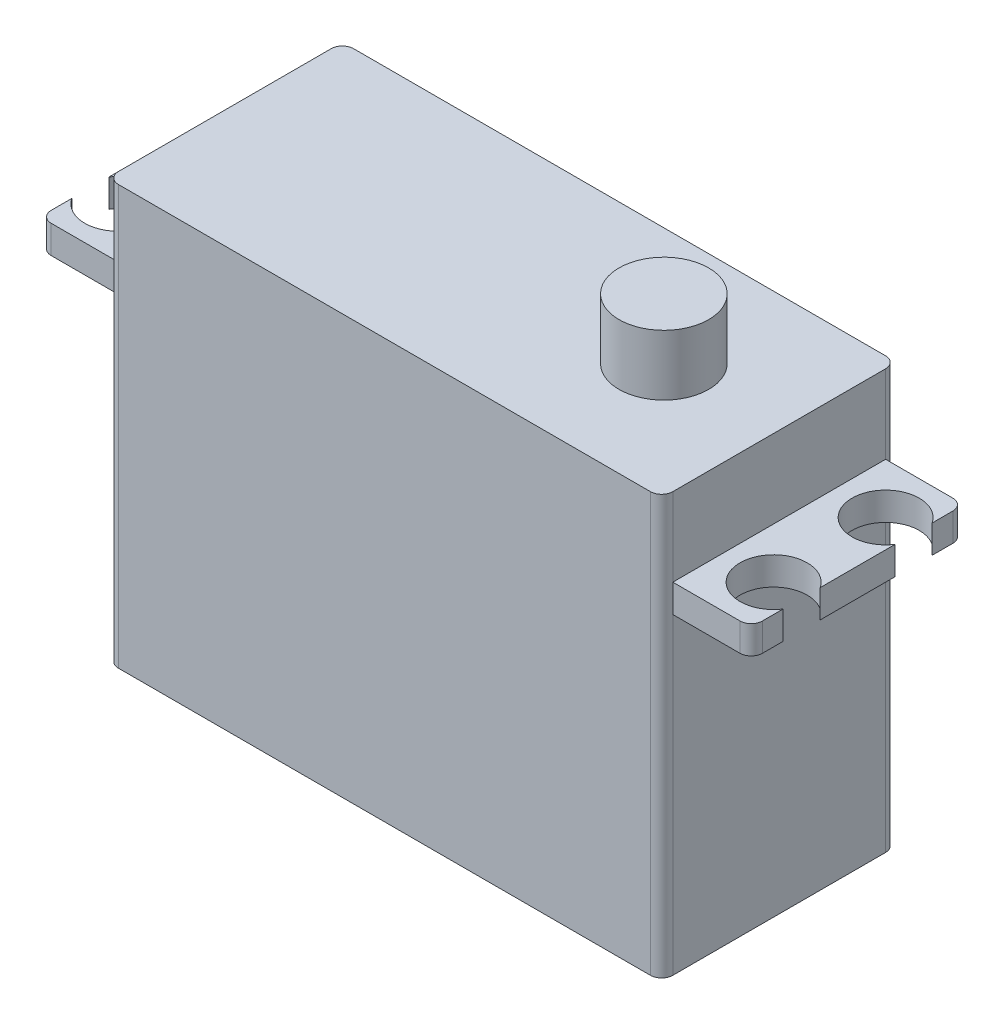
SolidWorks part; units mm, degrees
ref_plane "Front" through (0, 0, 0) normal (0, 0, 1) x (1, 0, 0)
ref_plane "Top" through (0, 0, 0) normal (0, 1, 0) x (1, 0, 0)
ref_plane "Right" through (0, 0, 0) normal (1, 0, 0) x (0, 0, -1)
sketch "草图1" plane through (0, 0, 0) normal (0, 1, 0) x (1, 0, 0)
  line L0 (0, 0) -> (0, 10.5) construction
  line L1 (-24.75, 10.5) -> (24.75, 10.5) construction
  line L2 (24.75, 10.5) -> (24.75, -10.5) construction
  line L3 (0, 0) -> (24.75, 0) construction
  line L4 (-24.75, 10.5) -> (-24.75, -10.5) construction
  line L5 (-24.75, -10.5) -> (24.75, -10.5) construction
  line L6 (-24.75, -10.5) -> (24.75, -10.5)
  line L7 (24.75, -10.5) -> (24.75, 10.5)
  line L8 (24.75, 10.5) -> (-24.75, 10.5)
  line L9 (-24.75, 10.5) -> (-24.75, -10.5)
  point P9 (-24.75, 0)
extrude "凸台-拉伸1" add sketch "草图1" along normal blind 30.4
sketch "草图2" plane through (24.75, 0, 0) normal (1, 0, 0) x (0, 0, -1)
  line L0 (0, 30.4) -> (0, 27.9) construction
  line L1 (-10.5, 30.4) -> (10.5, 30.4) construction
  line L2 (-9.5, 27.9) -> (9.5, 27.9) construction
  line L3 (-9.5, 27.9) -> (9.5, 27.9)
  line L4 (9.5, 27.9) -> (9.5, 30.4)
  line L5 (9.5, 30.4) -> (-9.5, 30.4)
  line L6 (-9.5, 30.4) -> (-9.5, 27.9)
extrude "凸台-拉伸2" add sketch "草图2" along normal blind 7
sketch "草图3" plane through (0, 30.4, 0) normal (0, 1, 0) x (1, 0, 0)
  line L0 (-24.75, 10.5) -> (-24.75, -10.5)
  line L1 (-24.75, -10.5) -> (24.75, -10.5)
  line L2 (24.75, -10.5) -> (24.75, 10.5)
  line L3 (24.75, 10.5) -> (-24.75, 10.5)
extrude "凸台-拉伸3" add sketch "草图3" along normal blind 7
sketch "草图4" plane through (0, 30.4, 0) normal (0, 1, 0) x (1, 0, 0)
  line L0 (24.75, 0) -> (31.75, 0) construction
  line L1 (24.75, -10.5) -> (24.75, 10.5) construction
  line L2 (31.75, 9.5) -> (31.75, -9.5) construction
  line L3 (24.75, 0) -> (24.75, 5) construction
  line L4 (24.75, -9.5) -> (24.75, 9.5) construction
  line L5 (24.75, 5) -> (29.25, 5) construction
  circle A0 centre (29.25, 5) radius 3
  circle A1 centre (29.25, -5) radius 3
extrude "切除-拉伸1" cut sketch "草图4" against normal blind 7
sketch "草图5" plane through (0, 37.4, 0) normal (0, 1, 0) x (1, 0, 0)
  line L0 (24.75, 0) -> (14.45, 0) construction
  line L1 (24.75, -10.5) -> (24.75, 10.5) construction
  circle A0 centre (14.45, 0) radius 4
extrude "凸台-拉伸4" add sketch "草图5" along normal blind 5.4
mirror "镜向2" about plane through (0, 0, 0) normal (1, 0, 0) of "切除-拉伸1", "凸台-拉伸2"
fillet "圆角1" radius 1 1 edges at (24.75, 18.7, -10.5)
fillet "圆角2" radius 1 1 edges at (24.75, 18.7, 10.5)
fillet "圆角3" radius 1 1 edges at (-24.75, 18.7, 10.5)
fillet "圆角4" radius 1 1 edges at (-24.75, 18.7, -10.5)
fillet "圆角5" radius 1 1 edges at (-31.75, 29.15, -9.5)
fillet "圆角6" radius 1 1 edges at (-31.75, 29.15, 9.5)
fillet "圆角7" radius 1 1 edges at (31.75, 29.15, 9.5)
fillet "圆角8" radius 1 1 edges at (31.75, 29.15, -9.5)
